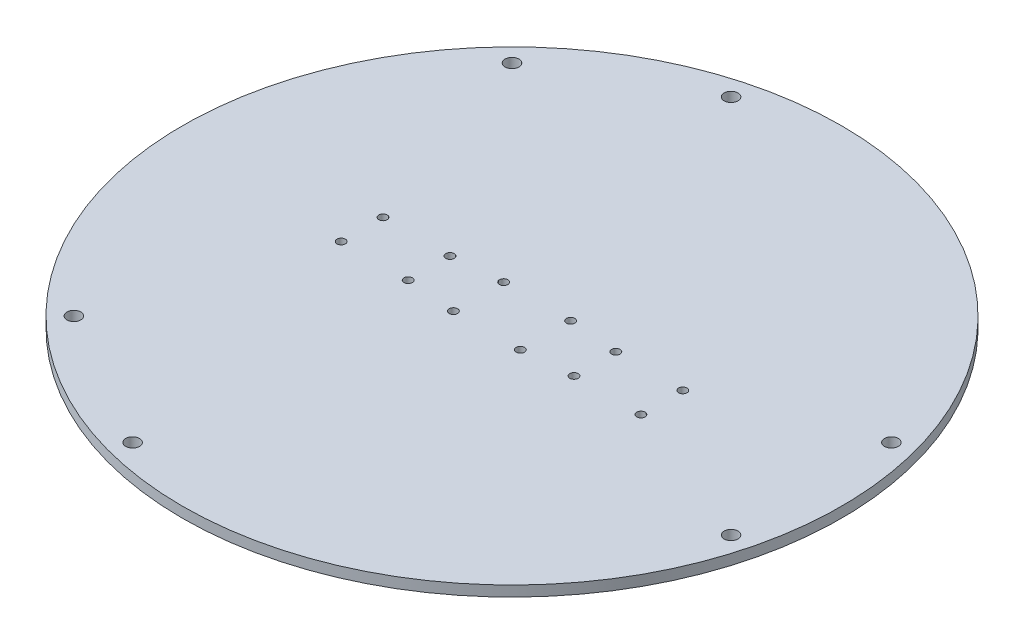
SolidWorks part; units mm, degrees
ref_plane "Front Plane" through (0, 0, 0) normal (0, 0, 1) x (1, 0, 0)
ref_plane "Top Plane" through (0, 0, 0) normal (0, 1, 0) x (1, 0, 0)
ref_plane "Right Plane" through (0, 0, 0) normal (1, 0, 0) x (0, 0, -1)
sketch "Sketch1" plane through (0, 0, 0) normal (0, 1, 0) x (1, 0, 0)
  line L0 (0, 100) -> (0, 0) construction
  line L1 (0, 0) -> (50, 86.6025) construction
  line L2 (-100, 0) -> (100, 0) construction
  line L3 (-10.16, 7.62) -> (10.16, 7.62) construction
  line L4 (-10.16, 7.62) -> (-10.16, -7.62) construction
  line L5 (-10.16, -7.62) -> (10.16, -7.62) construction
  line L6 (10.16, 7.62) -> (10.16, -7.62) construction
  line L7 (-10.16, 7.62) -> (10.16, -7.62) construction
  line L8 (-10.16, -7.62) -> (10.16, 7.62) construction
  line L9 (-25.16, -6.35) -> (-45.48, 6.35) construction
  line L10 (25.16, 6.35) -> (45.48, 6.35) construction
  line L11 (25.16, 6.35) -> (25.16, -6.35) construction
  line L12 (25.16, -6.35) -> (45.48, -6.35) construction
  line L13 (45.48, 6.35) -> (45.48, -6.35) construction
  line L14 (25.16, 6.35) -> (45.48, -6.35) construction
  line L15 (25.16, -6.35) -> (45.48, 6.35) construction
  line L16 (-25.16, 6.35) -> (-45.48, -6.35) construction
  line L17 (-45.48, 6.35) -> (-45.48, -6.35) construction
  line L18 (-25.16, -6.35) -> (-45.48, -6.35) construction
  line L19 (-25.16, 6.35) -> (-25.16, -6.35) construction
  line L20 (-25.16, 6.35) -> (-45.48, 6.35) construction
  line L21 (0, 0) -> (96.5926, 25.8819) construction
  line L22 (0, 0) -> (50, -86.6025) construction
  circle A0 centre (0, 0) radius 100
  circle A12 centre (-10.16, 7.62) radius 1.27
  circle A13 centre (-10.16, -7.62) radius 1.27
  circle A14 centre (10.16, -7.62) radius 1.27
  circle A15 centre (10.16, 7.62) radius 1.27
  circle A16 centre (25.16, 6.35) radius 1.27
  circle A17 centre (25.16, -6.35) radius 1.27
  circle A18 centre (45.48, -6.35) radius 1.27
  circle A19 centre (45.48, 6.35) radius 1.27
  circle A20 centre (-45.48, 6.35) radius 1.27
  circle A21 centre (-45.48, -6.35) radius 1.27
  circle A22 centre (-25.16, -6.35) radius 1.27
  circle A23 centre (-25.16, 6.35) radius 1.27
  circle A24 centre (90.797, 24.329) radius 2.1
  circle A25 centre (90.797, -24.329) radius 2.1
  circle A26 centre (-66.468, 66.468) radius 2.1
  circle A27 centre (-24.329, 90.797) radius 2.1
  circle A28 centre (-24.329, -90.797) radius 2.1
  circle A29 centre (-66.468, -66.468) radius 2.1
  point P27 (35.32, 0)
  point P44 (-35.32, 0)
  dimension "D1" = 200
  dimension "D3" = 60
  dimension "D6" = 2.54
  dimension "D13" = 4.2
  dimension "D2" = 20.32
  dimension "D4" = 60
  dimension "D5" = 15.24
  dimension "D7" = 12.7
  dimension "D8" = 20.32
  dimension "D9" = 15
  dimension "D11" = 90
  dimension "D12" = 15
  dimension "D14" = 6
extrude "Boss-Extrude1" add sketch "Sketch1" along normal blind 3.175
